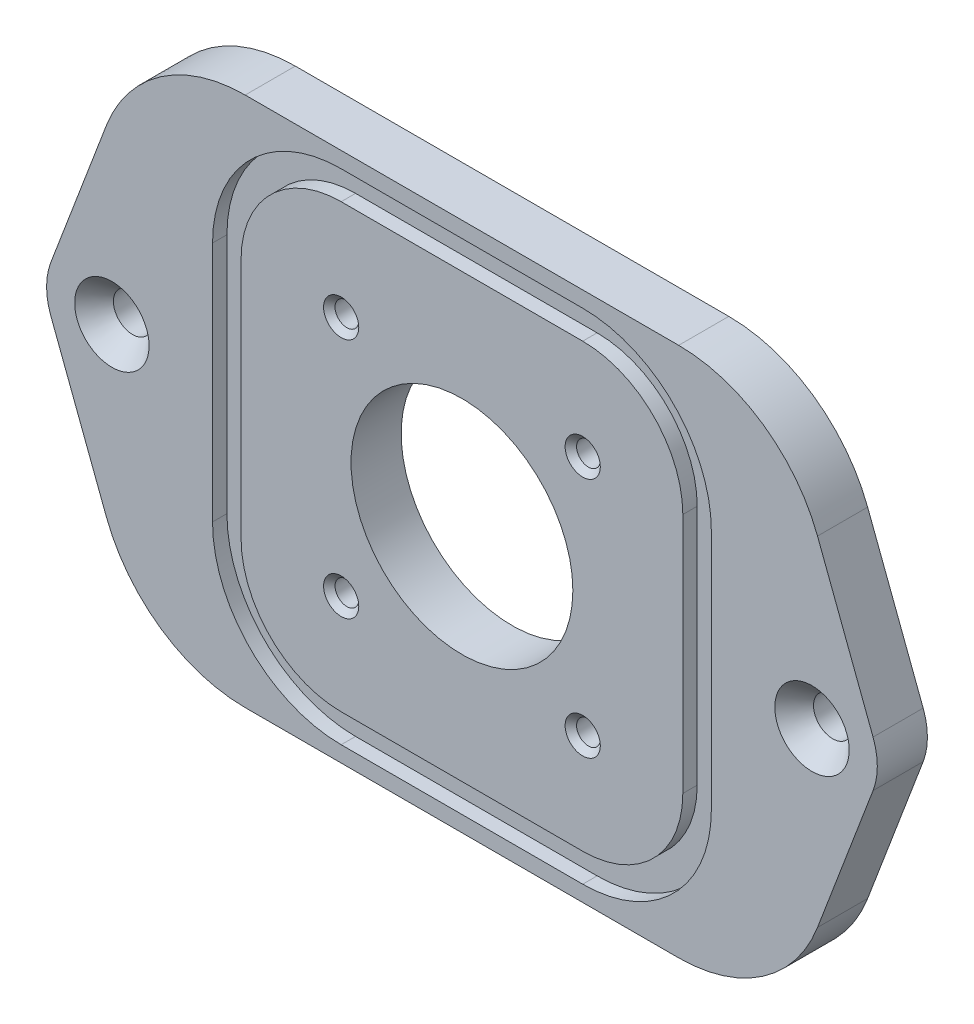
SolidWorks part; units mm, degrees
material "ASTM A36 Steel"
ref_plane "Front Plane" through (0, 0, 0) normal (0, 0, 1) x (1, 0, 0)
ref_plane "Top Plane" through (0, 0, 0) normal (0, 1, 0) x (1, 0, 0)
ref_plane "Right Plane" through (0, 0, 0) normal (1, 0, 0) x (0, 0, -1)
ref_axis "Axis1" through (0, 0, -5.014) along (0, 0, 1)
sketch "Sketch1" plane through (0, 0, 0) normal (0, 0, 1) x (1, 0, 0)
  line L0 (0, 18.9512) -> (0, 38.7973) construction
  line L1 (-20.6502, 25.273) -> (20.6502, 25.273)
  line L3 (-20.6502, -25.273) -> (20.6502, -25.273)
  line L4 (33.877, 16.1464) -> (39.1681, 2.2086)
  line L5 (39.1681, -2.2086) -> (33.877, -16.1464)
  line L6 (-39.1681, -2.2086) -> (-33.877, -16.1464)
  line L7 (-33.877, 16.1464) -> (-39.1681, 2.2086)
  circle A0 centre (0, 0) radius 10.5664
  arc A1 (20.6502, 25.273) -> (33.877, 16.1464) centre (20.6502, 11.1252) cw
  arc A2 (39.1681, 2.2086) -> (39.1681, -2.2086) centre (33.3502, 0) cw
  arc A3 (33.877, -16.1464) -> (20.6502, -25.273) centre (20.6502, -11.1252) cw
  arc A4 (-33.877, -16.1464) -> (-20.6502, -25.273) centre (-20.6502, -11.1252) ccw
  arc A5 (-39.1681, 2.2086) -> (-39.1681, -2.2086) centre (-33.3502, 0) ccw
  arc A6 (-20.6502, 25.273) -> (-33.877, 16.1464) centre (-20.6502, 11.1252) ccw
  dimension "D2" = 21.1328
  dimension "D4" = 14.1478
  dimension "D5" = 33.3502
  dimension "D6" = 6.223
  dimension "D1" = 50.546
  dimension "D3" = 20.6502
  dimension "D7" = 11.1252
extrude "Boss-Extrude1" add sketch "Sketch1" against normal blind 4.7752
hole_wizard "#4-40 Tapped Hole1" positions "Sketch3" profile "Sketch2" tap size "#4-40" standard "Ansi Inch" end condition up to next
sketch "Sketch3" plane through (0, 0, 0) normal (0, 0, 1) x (1, 0, 0)
  point P0 (11.5062, 11.5062)
  dimension "D1" = 16.2722
sketch "Sketch2" plane through (11.5062, 11.5062, 0) normal (1, 0, 0) x (0, -1, 0)
  line L0 (0, 0) -> (0, 4.7752)
  line L1 (0, 4.7752) -> (1.6764, 4.7752)
  line L2 (1.1303, 4.2291) -> (1.1303, 0.5461)
  line L3 (1.1303, 0.5461) -> (1.6764, 0)
  line L5 (1.6764, 0) -> (0, 0)
  line L6 (-1.1303, 0.5461) -> (-1.6764, 0) construction
  line L7 (1.6764, 4.7752) -> (1.1303, 4.2291)
  line L8 (-1.6764, 4.7752) -> (-1.1303, 4.2291) construction
  line L11 (0, -6.35) -> (0, 107.95) construction
  dimension "Thread Major Dia." = 2.2606
  dimension "Thru Tap Drill Depth" = 4.7752
  dimension "Near C'Sink Dia." = 3.3528
  dimension "Near C'Sink Angle" = 90
  dimension "Far C'Sink Dia." = 3.3528
  dimension "Far C'Sink Angle" = 90
pattern_circular "CirPattern1" count 4 over 360 about axis through (0, 0, -5.014) along (0, 0, 1) of "#4-40 Tapped Hole1"
hole_wizard "CSK for #6 Flat Head Machine Screw1" positions "Sketch5" profile "Sketch4" countersink size "#6" standard "Ansi Inch" end condition through all
sketch "Sketch5" plane through (0, 0, 0) normal (0, 0, 1) x (1, 0, 0)
  point P0 (33.3502, 0)
  point P1 (-33.3502, 0)
sketch "Sketch4" plane through (33.3502, 0, 0) normal (1, 0, 0) x (0, -1, 0)
  line L0 (0, 0) -> (0, 4.7752)
  line L1 (0, 4.7752) -> (1.8288, 4.7752)
  line L2 (1.8288, 4.7752) -> (1.8288, 1.9723)
  line L3 (1.8288, 1.9723) -> (3.5433, 0)
  line L5 (3.5433, 0) -> (0, 0)
  line L6 (-1.8288, 1.9723) -> (-3.5433, 0) construction
  line L11 (0, -6.35) -> (0, 107.95) construction
  dimension "Thru Hole Dia." = 3.6576
  dimension "Thru Hole Depth" = 4.7752
  dimension "Near C'Sink Dia." = 7.0866
  dimension "Near C'Sink Angle" = 82
sketch "Sketch6" plane through (0, 0, 0) normal (0, 0, 1) x (1, 0, 0)
  line L0 (21.0439, 11.5062) -> (21.0439, -11.5062)
  line L1 (-11.5062, 22.4155) -> (11.5062, 22.4155) construction
  line L2 (-22.4155, 11.5062) -> (-22.4155, -11.5062) construction
  line L3 (-11.5062, -22.4155) -> (11.5062, -22.4155) construction
  line L4 (22.4155, 11.5062) -> (22.4155, -11.5062) construction
  line L5 (-11.5062, -21.0439) -> (11.5062, -21.0439)
  line L6 (-21.0439, 11.5062) -> (-21.0439, -11.5062)
  line L7 (-11.5062, 21.0439) -> (11.5062, 21.0439)
  line L8 (23.7617, 11.5062) -> (23.7617, -11.5062)
  line L9 (-11.5062, -23.7617) -> (11.5062, -23.7617)
  line L10 (-23.7617, 11.5062) -> (-23.7617, -11.5062)
  line L11 (-11.5062, 23.7617) -> (11.5062, 23.7617)
  arc A0 (-22.4155, -11.5062) -> (-11.5062, -22.4155) centre (-11.5062, -11.5062) ccw construction
  arc A1 (-11.5062, 22.4155) -> (-22.4155, 11.5062) centre (-11.5062, 11.5062) ccw construction
  arc A2 (11.5062, 22.4155) -> (22.4155, 11.5062) centre (11.5062, 11.5062) cw construction
  arc A3 (11.5062, -22.4155) -> (22.4155, -11.5062) centre (11.5062, -11.5062) ccw construction
  arc A4 (11.5062, -21.0439) -> (21.0439, -11.5062) centre (11.5062, -11.5062) ccw
  arc A5 (-21.0439, -11.5062) -> (-11.5062, -21.0439) centre (-11.5062, -11.5062) ccw
  arc A6 (-11.5062, 21.0439) -> (-21.0439, 11.5062) centre (-11.5062, 11.5062) ccw
  arc A7 (11.5062, 21.0439) -> (21.0439, 11.5062) centre (11.5062, 11.5062) cw
  arc A8 (11.5062, -23.7617) -> (23.7617, -11.5062) centre (11.5062, -11.5062) ccw
  arc A9 (-23.7617, -11.5062) -> (-11.5062, -23.7617) centre (-11.5062, -11.5062) ccw
  arc A10 (-11.5062, 23.7617) -> (-23.7617, 11.5062) centre (-11.5062, 11.5062) ccw
  arc A11 (11.5062, 23.7617) -> (23.7617, 11.5062) centre (11.5062, 11.5062) cw
  point P12 (22.4155, 0)
  point P13 (0, 22.4155)
  dimension "D1" = 9.5377
  dimension "D2" = 44.831
  dimension "D3" = 1.3716
  dimension "D4" = 2.7178
extrude "Cut-Extrude1" cut sketch "Sketch6" against normal blind 1.3716
